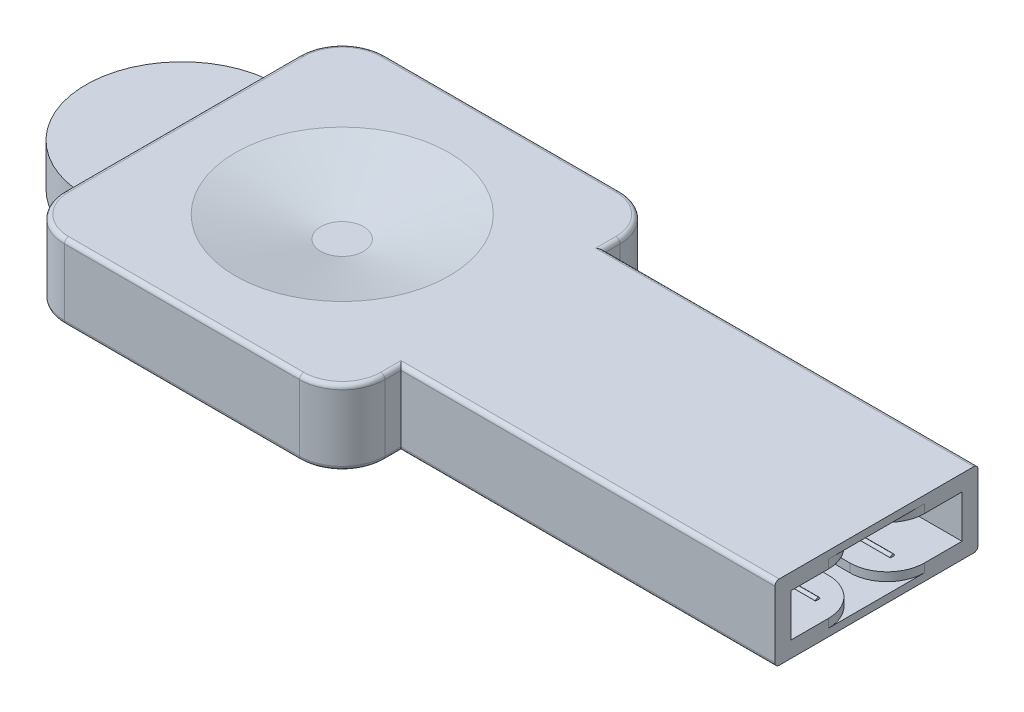
SolidWorks part; units mm, degrees
ref_plane "前视基准面" through (0, 0, 0) normal (0, 0, 1) x (1, 0, 0)
ref_plane "上视基准面" through (0, 0, 0) normal (0, 1, 0) x (1, 0, 0)
ref_plane "右视基准面" through (0, 0, 0) normal (1, 0, 0) x (0, 0, -1)
sketch "草图1" plane through (0, 0, 0) normal (0, 1, 0) x (1, 0, 0)
  line L0 (7.5, 7.5) -> (7.5, -7.5)
  line L1 (7.5, 7.5) -> (-7.5, 7.5)
  line L2 (7.5, -7.5) -> (-7.5, -7.5)
  line L3 (-7.5, 7.5) -> (-7.5, -7.5)
  line L4 (7.5, 7.5) -> (-7.5, -7.5) construction
  line L5 (7.5, -7.5) -> (-7.5, 7.5) construction
  point P1 (0, 0)
  dimension "D1" = 15
  dimension "D2" = 15
extrude "凸台-拉伸1" add sketch "草图1" along normal blind 1.75 and the other way blind 1.75
sketch "草图2" plane through (0, 0, 0) normal (0, 1, 0) x (1, 0, 0)
  line L0 (-7.5, 7.5) -> (-7.5, -7.5) construction
  circle A0 centre (-7.5, 0) radius 4.5
  dimension "D1" = 9
extrude "凸台-拉伸2" add sketch "草图2" along normal blind 1 and the other way blind 1
sketch "草图3" plane through (0, 0, 0) normal (0, 1, 0) x (1, 0, 0)
  line L0 (7.5, 0) -> (25, 0) construction
  line L1 (7.5, -7.5) -> (7.5, 7.5) construction
  line L2 (7.5, -4.75) -> (25, -4.75)
  line L3 (7.5, 4.75) -> (25, 4.75)
  line L4 (7.5, 4.75) -> (7.5, -4.75)
  line L5 (25, 4.75) -> (25, -4.75)
  dimension "D1" = 17.5
  dimension "D2" = 4.75
  dimension "D3" = 4.75
extrude "凸台-拉伸3" add sketch "草图3" along normal blind 1.75 and the other way blind 1.75
sketch "草图4" plane through (0, 1.75, 0) normal (0, 1, 0) x (1, 0, 0)
  line L0 (0, 0) -> (-5, 0) construction
  circle A0 centre (0, 0) radius 5
  dimension "D1" = 10
ref_plane "基准面1" through (0, 0.75, 0) normal (0, 1, 0) x (1, 0, 0)
sketch "草图5" plane through (0, 0.75, 0) normal (0, 1, 0) x (1, 0, 0)
  line L0 (0, 0) -> (-1, 0) construction
  circle A0 centre (0, 0) radius 1
  dimension "D1" = 2
loft "切除-放样1" cut profiles "草图4", "草图5" connector at (-4.9999, 1.75, 0.0377) connector at (-1, 0.75, -0.0019)
mirror "镜向1" about plane through (0, 0, 0) normal (0, 1, 0) of "切除-放样1"
sketch "草图6" plane through (25, 0, 0) normal (1, 0, 0) x (0, 0, -1)
  line L0 (4, 1) -> (4, -1)
  line L1 (4, 1) -> (-4, 1)
  line L2 (4, -1) -> (-4, -1)
  line L3 (-4, 1) -> (-4, -1)
  line L4 (4, 1) -> (-4, -1) construction
  line L5 (4, -1) -> (-4, 1) construction
  point P1 (0, 0)
  dimension "D1" = 8
  dimension "D2" = 2
extrude "切除-拉伸1" cut sketch "草图6" against normal blind 6
sketch "草图7" plane through (25, 0, 0) normal (1, 0, 0) x (0, 0, -1)
  line L0 (0.5, 1.4) -> (0.5, -1.4)
  line L1 (0.5, 1.4) -> (-0.5, 1.4)
  line L2 (0.5, -1.4) -> (-0.5, -1.4)
  line L3 (-0.5, 1.4) -> (-0.5, -1.4)
  line L4 (0.5, 1.4) -> (-0.5, -1.4) construction
  line L5 (0.5, -1.4) -> (-0.5, 1.4) construction
  point P1 (0, 0)
  dimension "D1" = 1
  dimension "D2" = 2.8
extrude "切除-拉伸2" cut sketch "草图7" against normal blind 6
sketch "草图8" plane through (19, 0, 0) normal (1, 0, 0) x (0, 0, -1)
  line L0 (0, 0) -> (0, -1) construction
  line L1 (0, -1) -> (-1.75, -1) construction
  line L2 (-4, -1) -> (-0.5, -1) construction
  circle A0 centre (-1.75, -1) radius 0.1
  dimension "D3" = 0.2
  dimension "D1" = 1
  dimension "D2" = 1.75
extrude "凸台-拉伸4" add sketch "草图8" along normal blind 5
mirror "镜向2" about plane through (0, 0, 0) normal (0, 0, 1) of "凸台-拉伸4"
mirror "镜向3" about plane through (0, 0, 0) normal (0, 1, 0) of "凸台-拉伸4", "镜向2"
fillet "圆角1" radius 1.75 4 edges at (25, 1.2, -0.5) (25, 1.2, 0.5) (25, -1.2, -0.5) (25, -1.2, 0.5)
fillet "圆角2" radius 0.2 14 edges at (-7.5, -1.75, 0) (0, -1.75, 7.5) (0, -1.75, -7.5) (0, 1.75, -7.5) (0, 1.75, 7.5) (-7.5, 1.75, 0)
fillet "圆角3" radius 2 12 edges at (7.4414, 1.6914, -7.4414) (7.4414, -1.6914, -7.4414) (-7.4414, 1.6914, -7.4414) (-7.4414, -1.6914, -7.4414) (-7.4414, 1.6914, 7.4414) (-7.4414, -1.6914, 7.4414) (7.4414, 1.6914, 7.4414) (7.4414, -1.6914, 7.4414) (7.5, 0, 7.5) (-7.5, 0, 7.5) (-7.5, 0, -7.5) (7.5, 0, -7.5)
